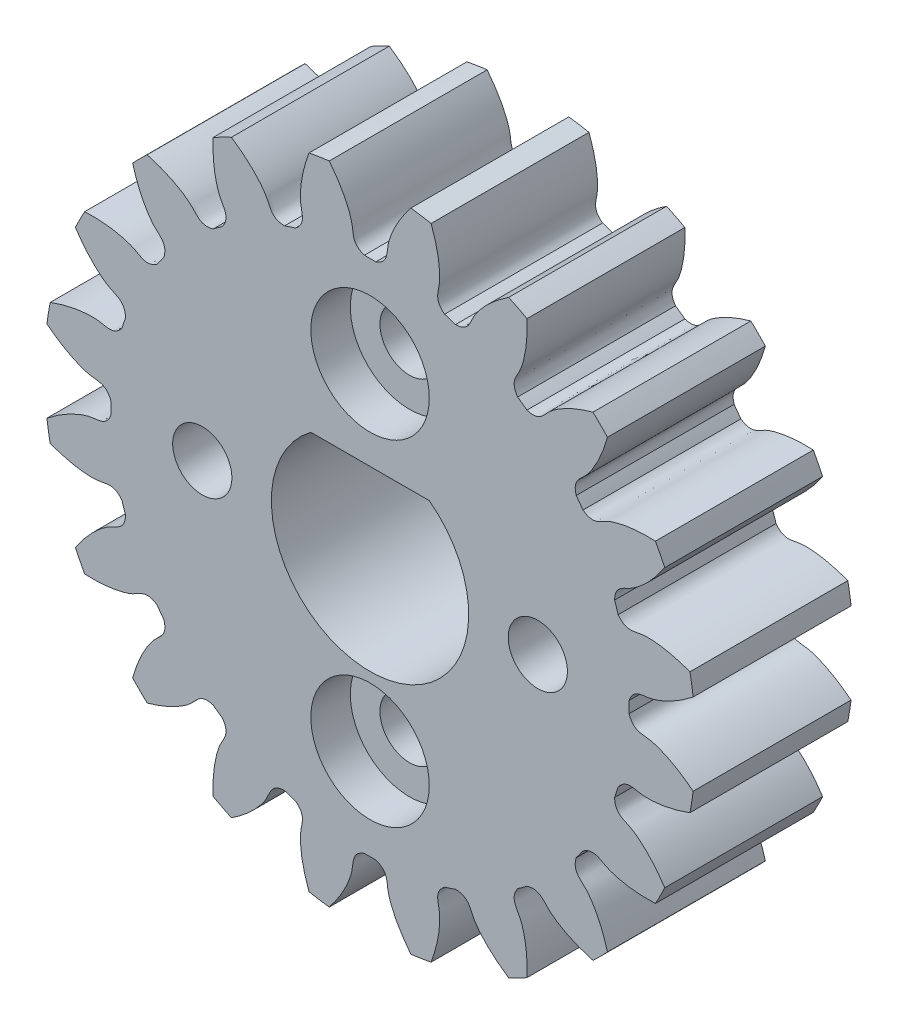
SolidWorks part; units mm, degrees
material "1060 合金"
ref_plane "前视基准面" through (0, 0, 0) normal (0, 0, 1) x (1, 0, 0)
ref_plane "上视基准面" through (0, 0, 0) normal (0, 1, 0) x (1, 0, 0)
ref_plane "右视基准面" through (0, 0, 0) normal (1, 0, 0) x (0, 0, -1)
sketch "草图1" plane through (0, 0, 0) normal (0, 0, 1) x (1, 0, 0)
  circle A0 centre (0, 0) radius 16.5
extrude "凸台-拉伸1" add sketch "草图1" along normal blind 8
ref_axis "基准轴1" through (0, 0, 8) along (0, 0, -1)
sketch "草图2" plane through (0, 0, 0) normal (0, 0, 1) x (1, 0, 0)
  line L0 (0, 0) -> (0, 16.5) construction
  circle A0 centre (0, 0) radius 16.5 construction
  arc A1 (0.29, 13.1218) -> (-0.29, 13.1218) centre (0, 0) ccw
  arc A2 (4.7717, 18.7474) -> (-4.7717, 18.7474) centre (0, 0) ccw
  spline S0 degree 3 poles (0.29, 13.1218) (0.9168, 13.3402) (0.8356, 13.7807) (0.9193, 14.205) (0.9283, 14.2463) (0.9395, 14.293) (0.9529, 14.3448) (0.969, 14.4018) (0.9878, 14.4638) (1.0095, 14.5309) (1.0345, 14.6028) (1.0629, 14.6795) (1.0948, 14.7608) (1.1305, 14.8467) (1.1702, 14.9371) (1.2141, 15.0317) (1.2623, 15.1305) (1.315, 15.2334) (1.3725, 15.3401) (1.4349, 15.4506) (1.5023, 15.5646) (1.575, 15.6821) (1.653, 15.8029) (1.7366, 15.9267) (1.826, 16.0534) (1.9211, 16.1829) (2.0223, 16.3149) (2.1296, 16.4493) (2.2432, 16.5859) (2.3632, 16.7244) (2.4897, 16.8646) (2.6229, 17.0065) (2.7628, 17.1496) (2.9095, 17.2939) (3.0632, 17.4391) (3.224, 17.585) (3.3918, 17.7313) (3.567, 17.8779) (3.7493, 18.0245) (3.9391, 18.1709) (4.1363, 18.3167) (4.4122, 18.5125) (4.6259, 18.6545) (4.7717, 18.7474) knots 0 0 0 0 0.165916 0.170906 0.176664 0.183189 0.190482 0.198542 0.207371 0.216967 0.22733 0.238462 0.250361 0.263027 0.276462 0.290664 0.305634 0.321371 0.337876 0.355149 0.37319 0.391998 0.411574 0.431917 0.453028 0.474907 0.497554 0.520968 0.54515 0.570099 0.595817 0.622302 0.649554 0.677575 0.706363 0.735918 0.766242 0.797333 0.829191 0.861818 0.895212 0.929373 1 1 1 1
  spline S1 degree 3 poles (-0.29, 13.1218) (-0.9168, 13.3402) (-0.8356, 13.7807) (-0.9193, 14.205) (-0.9283, 14.2463) (-0.9395, 14.293) (-0.9529, 14.3448) (-0.969, 14.4018) (-0.9878, 14.4638) (-1.0095, 14.5309) (-1.0345, 14.6028) (-1.0629, 14.6795) (-1.0948, 14.7608) (-1.1305, 14.8467) (-1.1702, 14.9371) (-1.2141, 15.0317) (-1.2623, 15.1305) (-1.315, 15.2334) (-1.3725, 15.3401) (-1.4349, 15.4506) (-1.5023, 15.5646) (-1.575, 15.6821) (-1.653, 15.8029) (-1.7366, 15.9267) (-1.826, 16.0534) (-1.9211, 16.1829) (-2.0223, 16.3149) (-2.1296, 16.4493) (-2.2432, 16.5859) (-2.3632, 16.7244) (-2.4897, 16.8646) (-2.6229, 17.0065) (-2.7628, 17.1496) (-2.9095, 17.2939) (-3.0632, 17.4391) (-3.224, 17.585) (-3.3918, 17.7313) (-3.567, 17.8779) (-3.7493, 18.0245) (-3.9391, 18.1709) (-4.1363, 18.3167) (-4.4122, 18.5125) (-4.6259, 18.6545) (-4.7717, 18.7474) knots 0 0 0 0 0.165916 0.170906 0.176664 0.183189 0.190482 0.198542 0.207371 0.216967 0.22733 0.238462 0.250361 0.263027 0.276462 0.290664 0.305634 0.321371 0.337876 0.355149 0.37319 0.391998 0.411574 0.431917 0.453028 0.474907 0.497554 0.520968 0.54515 0.570099 0.595817 0.622302 0.649554 0.677575 0.706363 0.735918 0.766242 0.797333 0.829191 0.861818 0.895212 0.929373 1 1 1 1
extrude "切除-拉伸1" cut sketch "草图2" along normal through all
pattern_circular "阵列(圆周)1" count 20 every 18 about axis through (0, 0, 8) along (0, 0, -1) of "切除-拉伸1"
sketch "草图3" plane through (0, 0, 0) normal (0, 0, 1) x (1, 0, 0)
  circle A0 centre (0, 0) radius 15 construction
  dimension "Dn" = 30
sketch "草图4" plane through (0, 0, 8) normal (0, 0, 1) x (1, 0, 0)
  line L0 (-3, 4) -> (3, 4)
  circle A0 centre (0, 0) radius 8.5 construction
  circle A1 centre (0, 8.5) radius 1.5
  circle A2 centre (8.5, 0) radius 1.5
  circle A3 centre (0, -8.5) radius 1.5
  circle A4 centre (-8.5, 0) radius 1.5
  arc A5 (-3, 4) -> (3, 4) centre (0, 0) ccw
  dimension "D1" = 17
  dimension "D2" = 3
  dimension "D3" = 3
  dimension "D4" = 3
  dimension "D5" = 3
  dimension "D6" = 10
  dimension "D7" = 4
extrude "切除-拉伸2" cut sketch "草图4" against normal blind 10
sketch "草图5" plane through (0, 0, 8) normal (0, 0, 1) x (1, 0, 0)
  circle A0 centre (0, 8.5) radius 3
  circle A1 centre (0, -8.5) radius 3
  dimension "D1" = 6
  dimension "D2" = 6
extrude "切除-拉伸3" cut sketch "草图5" against normal blind 2
